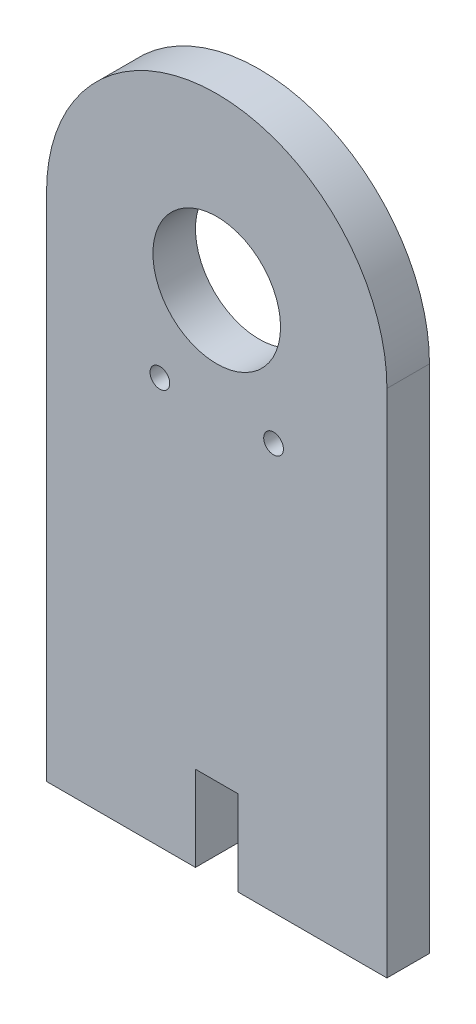
SolidWorks part; units mm, degrees
ref_plane "Front Plane" through (0, 0, 0) normal (0, 0, 1) x (1, 0, 0)
ref_plane "Top Plane" through (0, 0, 0) normal (0, 1, 0) x (1, 0, 0)
ref_plane "Right Plane" through (0, 0, 0) normal (1, 0, 0) x (0, 0, -1)
sketch "Sketch2" plane through (0, 0, 0) normal (0, 0, 1) x (1, 0, 0)
  line L1 (0, 0) -> (50.8, 0)
  line L2 (0, 0) -> (0, 76.2)
  line L4 (50.8, 0) -> (50.8, 76.2)
  arc A2 (50.8, 76.2) -> (0, 76.2) centre (25.4, 76.2) ccw
  dimension "D4" = 25.4
  dimension "D2" = 76.2
  dimension "D3" = 76.2
extrude "Boss-Extrude1" add sketch "Sketch2" along normal blind 6.35
sketch "Sketch3" plane through (0, 0, 6.35) normal (0, 0, 1) x (1, 0, 0)
  line L0 (0, 0) -> (50.8, 0) construction
  line L1 (22.225, 0) -> (28.575, 0)
  line L2 (22.225, 0) -> (22.225, 12.7)
  line L3 (22.225, 12.7) -> (28.575, 12.7)
  line L4 (28.575, 0) -> (28.575, 12.7)
  line L5 (0, 76.2) -> (0, 0) construction
  dimension "D1" = 22.225
  dimension "D3" = 12.7
extrude "Cut-Extrude1" cut sketch "Sketch3" against normal blind 6.35
sketch "Sketch4" plane through (0, 0, 6.35) normal (0, 0, 1) x (1, 0, 0)
  point P0 (25.4, 76.2)
  point P1 (16.9164, 60.6298)
  point P3 (33.8836, 60.6298)
  dimension "D1" = 8.4836
  dimension "D2" = 8.4836
  dimension "D3" = 15.5702
  dimension "D4" = 0
hole_wizard "3/4 (0.75) Diameter Hole1" positions "3DSketch1" profile "Sketch5" hole size "3/4" standard "ANSI Inch" end condition through all
sketch3d "3DSketch1"
  point P0 (25.4, 76.2, 6.35)
sketch "Sketch5" plane through (25.4, 76.2, 6.35) normal (1, 0, 0) x (0, -1, 0)
  line L0 (0, 0) -> (0, 6.35)
  line L1 (0, 6.35) -> (9.525, 6.35)
  line L2 (9.525, 6.35) -> (9.525, 0)
  line L5 (9.525, 0) -> (0, 0)
  line L11 (0, -6.35) -> (0, 107.95) construction
  dimension "Thru Hole Dia." = 19.05
  dimension "Thru Hole Depth" = 6.35
hole_wizard "#32 (0.116) Diameter Hole1" positions "Sketch6" profile "Sketch7" hole size "#32" standard "ANSI Inch" end condition through all
sketch "Sketch6" plane through (0, 0, 6.35) normal (0, 0, 1) x (1, 0, 0)
  point P0 (16.9164, 60.6298)
  point P3 (33.8836, 60.6298)
sketch "Sketch7" plane through (16.9164, 60.6298, 6.35) normal (1, 0, 0) x (0, -1, 0)
  line L0 (0, 0) -> (0, 6.35)
  line L1 (0, 6.35) -> (1.4732, 6.35)
  line L2 (1.4732, 6.35) -> (1.4732, 0)
  line L5 (1.4732, 0) -> (0, 0)
  line L11 (0, -6.35) -> (0, 107.95) construction
  dimension "Thru Hole Dia." = 2.9464
  dimension "Thru Hole Depth" = 6.35
equation "\"wheel_width\"= 2"
equation "\"wheel_height\"= 3"
equation "\"wheel_radius\"= \"wheel_width\" / 2"
equation "\"D1@Sketch2\"=\"wheel_width\""
equation "\"D3@Sketch2\"=\"wheel_height\""
equation "\"D2@Sketch2\"=\"wheel_height\""
equation "\"D4@Sketch2\"=\"wheel_radius\""
equation "\"D1@Sketch3\"=(\"wheel_width\"-\"cutout_thickness\")/2"
equation "\"cutout_thickness\"= 0.25"
equation "\"cutout_height\"= 0.5"
equation "\"D2@Sketch3\"=\"cutout_thickness\""
equation "\"D3@Sketch3\"=\"cutout_height\""
